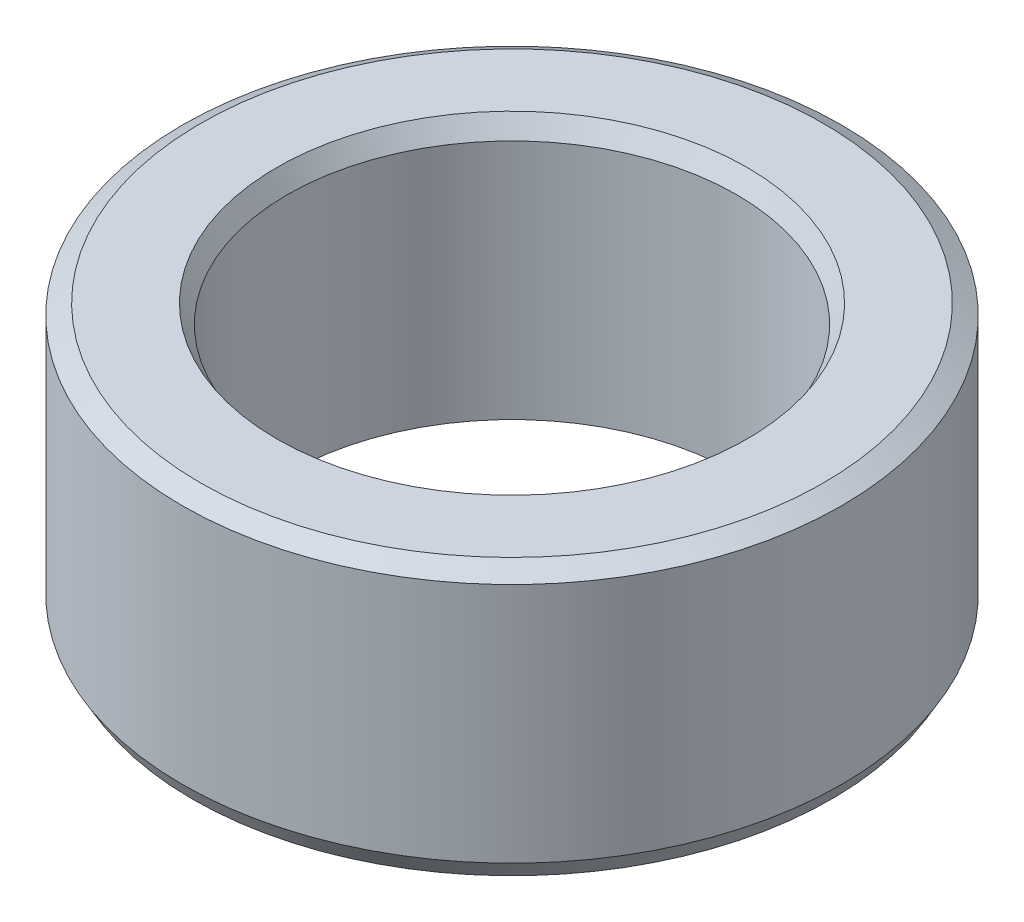
SolidWorks part; units mm, degrees
ref_plane "Front Plane" through (0, 0, 0) normal (0, 0, 1) x (1, 0, 0)
ref_plane "Top Plane" through (0, 0, 0) normal (0, 1, 0) x (1, 0, 0)
ref_plane "Right Plane" through (0, 0, 0) normal (1, 0, 0) x (0, 0, -1)
sketch "Sketch1" plane through (0, 0, 0) normal (0, 1, 0) x (1, 0, 0)
  circle A0 centre (0, 0) radius 45
  dimension "SLEEVE_OD" = 90
extrude "Boss-Extrude1" add sketch "Sketch1" along normal blind 36.8758
sketch "Sketch2" plane through (0, 0, 0) normal (0, 1, 0) x (1, 0, 0)
  circle A0 centre (0, 0) radius 30.6585
  dimension "BORE_D" = 61.3169
extrude "Cut-Extrude1" cut sketch "Sketch2" along normal through all
chamfer "Chamfer1" distance 1.441 angle 60 4 edges at (0, 36.8758, 30.6585) (0, 0, 30.6585) (0, 0, 45) (0, 36.8758, 45) first distance on face at (0, 36.8758, 30.6585) first distance on face at (0, 0, 30.6585) first distance on face at (0, 36.8758, 45)
